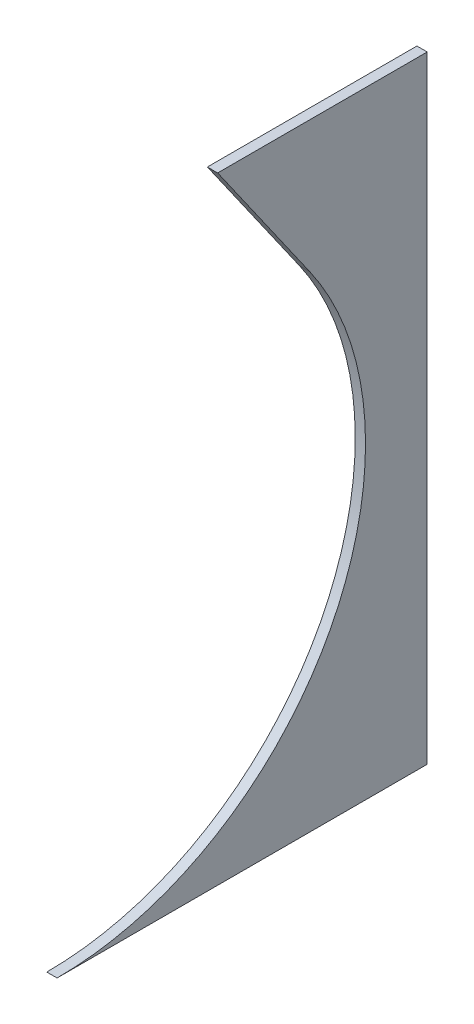
SolidWorks part; units mm, degrees
ref_plane "Front Plane" through (0, 0, 0) normal (0, 0, 1) x (1, 0, 0)
ref_plane "Top Plane" through (0, 0, 0) normal (0, 1, 0) x (1, 0, 0)
ref_plane "Right Plane" through (0, 0, 0) normal (1, 0, 0) x (0, 0, -1)
sketch "Sketch1" plane through (0, 0, 0) normal (1, 0, 0) x (0, 0, -1)
  line L0 (-95.25, 31.75) -> (133.35, 31.75) construction
  line L1 (-95.25, -158.75) -> (133.35, -158.75)
  line L2 (-95.25, -158.75) -> (-95.25, 222.25)
  line L3 (-95.25, 222.25) -> (133.35, 222.25)
  line L4 (133.35, -158.75) -> (133.35, 222.25)
  line L5 (-95.25, -158.75) -> (133.35, 222.25) construction
  line L6 (-95.25, 222.25) -> (133.35, -158.75) construction
  point P0 (0, 0)
  dimension "D1" = 228.6
  dimension "D2" = 381
extrude "Boss-Extrude1" add sketch "Sketch1" along normal blind 6.35
sketch "Sketch2" plane through (6.35, 0, 0) normal (1, 0, 0) x (0, 0, -1)
  line L0 (-95.25, 222.25) -> (-95.25, -158.75) construction
  line L1 (133.35, 222.25) -> (-95.25, 222.25) construction
  circle A0 centre (-95.25, 31.75) radius 190.5
  dimension "D1" = 381
  dimension "D2" = 0
  dimension "D3" = 190.5
extrude "Cut-Extrude1" cut sketch "Sketch2" against normal through all
sketch "Sketch3" plane through (6.35, 0, 0) normal (1, 0, 0) x (0, 0, -1)
  line L1 (60.7985, 141.0163) -> (-14.5807, 248.6689)
  line L2 (60.7985, 141.0163) -> (-203.4462, 141.0163)
  line L5 (-14.5807, 248.6689) -> (-203.4462, 248.6689)
  line L6 (-203.4462, 248.6689) -> (-203.4462, 141.0163)
  arc A0 (-95.25, -158.75) -> (-95.25, 222.25) centre (-95.25, 31.75) ccw construction
  dimension "D1" = 55
extrude "Cut-Extrude2" cut sketch "Sketch3" against normal through all
